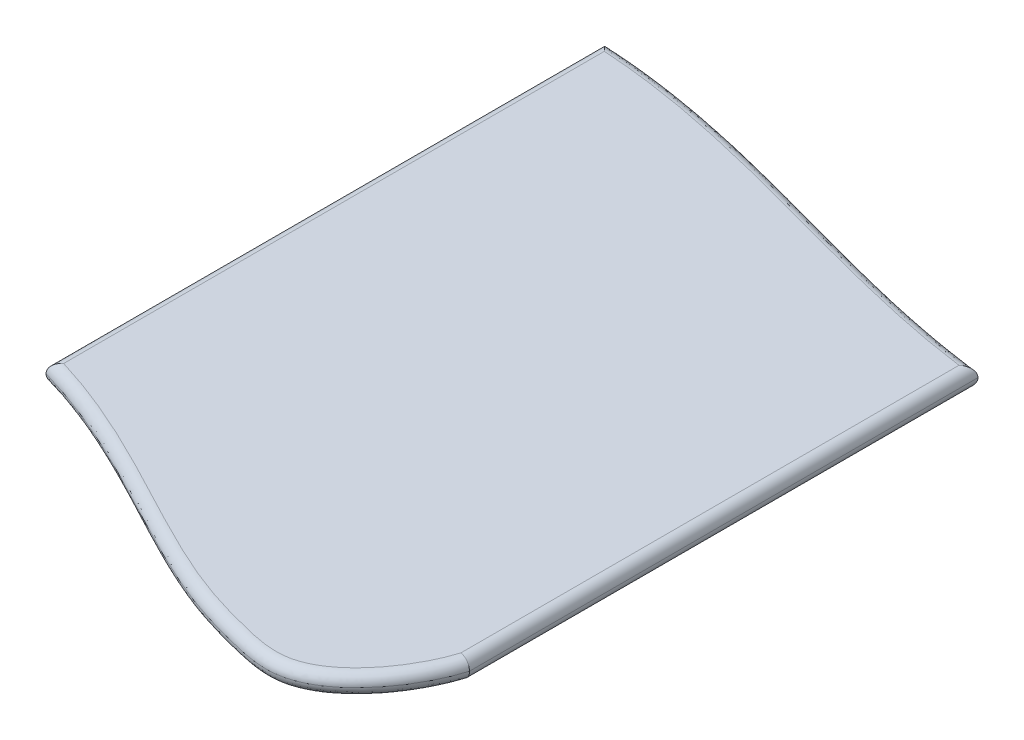
SolidWorks part; units mm, degrees
ref_plane "Front Plane" through (0, 0, 0) normal (0, 0, 1) x (1, 0, 0)
ref_plane "Top Plane" through (0, 0, 0) normal (0, 1, 0) x (1, 0, 0)
ref_plane "Right Plane" through (0, 0, 0) normal (1, 0, 0) x (0, 0, -1)
sketch "Sketch1" plane through (0, 0, 0) normal (0, 1, 0) x (1, 0, 0)
  line L0 (145.7228, 139.3487) -> (145.7228, 28.677)
  line L1 (238.6854, 120.2785) -> (238.6854, 19.5809)
  spline S0 degree 3 poles (145.7228, 139.3487) (177.6638, 137.9581) (207.1429, 124.1498) (238.6854, 120.2785) knots 0 0 0 0 1 1 1 1
  spline S1 degree 3 poles (238.6854, 19.5809) (236.4637, 12.0147) (226.669, -2.5947) (209.9236, 1.0186) (199.301, 4.1188) (186.5412, 9.9336) (169.1739, 19.4777) (154.8686, 26.0888) (145.7228, 28.677) knots 0 0 0 0 0.25421 0.351342 0.449635 0.564817 0.737481 1 1 1 1
extrude "Boss-Extrude1" add sketch "Sketch1" along normal blind 4
ref_axis "Axis2" through (145.7228, 2, -28.677) along (0, 0, -1)
ref_axis "Axis3" through (238.6854, 2, -19.5809) along (0, 0, -1)
fillet "Fillet1" radius 2 8 edges at (145.7228, 0, -84.0129) (238.6854, 0, -69.9297) (238.6854, 4, -69.9297) (145.7228, 4, -84.0129)
ref_axis "Axis4" through (238.6854, 2, -120.2785) along (0, 1, 0)
